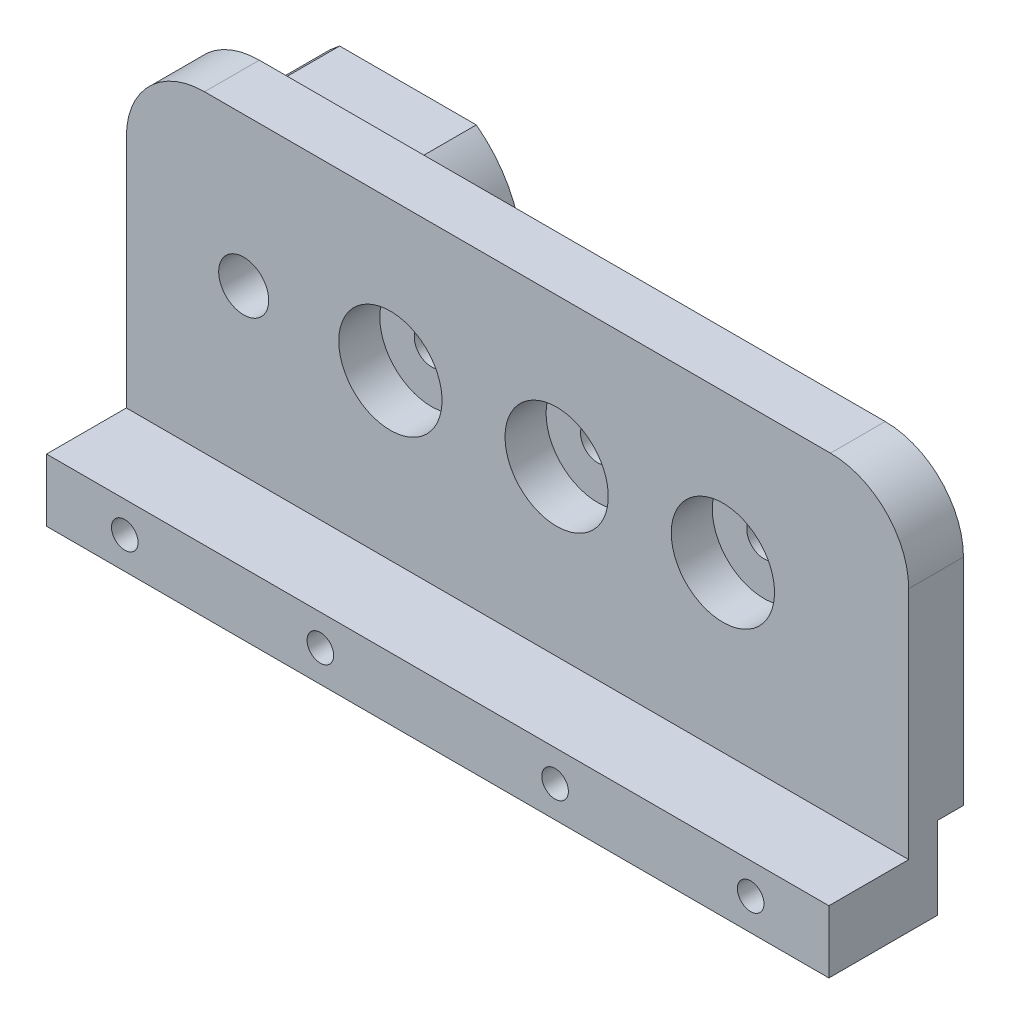
SolidWorks part; units mm, degrees
ref_plane "Front Plane" through (0, 0, 0) normal (0, 0, 1) x (1, 0, 0)
ref_plane "Top Plane" through (0, 0, 0) normal (0, 1, 0) x (1, 0, 0)
ref_plane "Right Plane" through (0, 0, 0) normal (1, 0, 0) x (0, 0, -1)
sketch "Sketch1" plane through (0, 0, 0) normal (0, 0, 1) x (1, 0, 0)
  line L1 (0, 0) -> (100, 0)
  line L2 (0, 0) -> (0, 48)
  line L3 (0, 48) -> (100, 48)
  line L4 (100, 0) -> (100, 48)
  dimension "D1" = 100
  dimension "D2" = 48
extrude "Boss-Extrude1" add sketch "Sketch1" along normal blind 7
sketch "Sketch2" plane through (0, 0, 7) normal (0, 0, 1) x (1, 0, 0)
  line L0 (0, 0) -> (100, 0) construction
  line L1 (0, 48) -> (0, 0) construction
  circle A0 centre (15, 29) radius 3.2
  circle A1 centre (33.75, 29) radius 2.2
  circle A2 centre (55, 29) radius 2.2
  circle A3 centre (76.25, 29) radius 2.2
  dimension "D1" = 4.4
  dimension "D2" = 18.75
  dimension "D3" = 21.25
  dimension "D4" = 21.25
  dimension "D5" = 29
  dimension "D6" = 15
  dimension "D7" = 6.4
extrude "Cut-Extrude1" cut sketch "Sketch2" against normal up to next
sketch "Sketch3" plane through (0, 0, 0) normal (0, 0, -1) x (-1, 0, 0)
  line L0 (0, 48) -> (0, 0) construction
  line L1 (-100, 0) -> (0, 0)
  line L2 (-100, 0) -> (-100, 8)
  line L3 (-100, 8) -> (0, 8)
  line L4 (0, 0) -> (0, 8)
  dimension "D1" = 8
extrude "Boss-Extrude2" add sketch "Sketch3" along normal blind 10.2
sketch "Sketch4" plane through (0, 0, 0) normal (0, 0, -1) x (-1, 0, 0)
  circle A0 centre (-76.25, 29) radius 6.6
  circle A1 centre (-55, 29) radius 6.6
  circle A2 centre (-33.75, 29) radius 6.6
  dimension "D1" = 13.2
extrude "Cut-Extrude2" cut sketch "Sketch4" against normal blind 5.25
sketch "Sketch5" plane through (0, 0, 7) normal (0, 0, 1) x (1, 0, 0)
  line L0 (35, 4.0521) -> (65, 4) construction
  line L1 (0, 0) -> (100, 0) construction
  circle A0 centre (35, 4.0521) radius 2.6
  circle A1 centre (65, 4) radius 2.6
  point P6 (50, 0)
  point P7 (50, 4.0261)
  dimension "D1" = 5.2
  dimension "D2" = 30
  dimension "D3" = 4
extrude "Cut-Extrude3" cut sketch "Sketch5" against normal blind 0.1
sketch "Sketch7" plane through (0, 0, 6.9) normal (0, 0, 1) x (1, 0, 0)
  circle A0 centre (35, 4.0521) radius 1.7
  circle A1 centre (65, 4) radius 1.7
  dimension "D1" = 3.4
extrude "Cut-Extrude4" cut sketch "Sketch7" against normal through all
sketch "Sketch8" plane through (0, 0, 7) normal (0, 0, 1) x (1, 0, 0)
  line L0 (10, 4.0521) -> (35, 4.0521) construction
  line L1 (0, 48) -> (0, 0) construction
  line L2 (100, 0) -> (100, 48) construction
  circle A0 centre (10, 4.0521) radius 1.7
  circle A1 centre (90, 4.0521) radius 1.7
  dimension "D1" = 3.4
  dimension "D2" = 10
  dimension "D3" = 10
extrude "Cut-Extrude5" cut sketch "Sketch8" against normal up to next
mirror "Mirror1" about plane through (0, 0, -10.2) normal (0, 0, 1) of bodies 110
delete or keep bodies "Body-Delete/Keep 1" type delete bodies bodies 110
sketch "Sketch9" plane through (100, 0, 0) normal (1, 0, 0) x (0, 0, -1)
  line L1 (27.4, 0) -> (24.1, 0)
  line L2 (27.4, 0) -> (27.4, 10.5)
  line L3 (27.4, 10.5) -> (24.1, 10.5)
  line L4 (24.1, 0) -> (24.1, 10.5)
  dimension "D1" = 10.5
  dimension "D2" = 3.3
extrude "Cut-Extrude6" cut sketch "Sketch9" against normal up to next
sketch "Sketch10" plane through (0, 0, -27.4) normal (0, 0, -1) x (-1, 0, 0)
  line L1 (-22.8594, 38.2) -> (-7.1406, 38.2)
  line L2 (-22.8594, 38.2) -> (-22.8594, 19.8) construction
  line L3 (-22.8594, 19.8) -> (-7.1406, 19.8)
  line L4 (-7.1406, 38.2) -> (-7.1406, 19.8) construction
  line L5 (-22.8594, 38.2) -> (-7.1406, 19.8) construction
  line L6 (-22.8594, 19.8) -> (-7.1406, 38.2) construction
  circle A0 centre (-15, 29) radius 12.1
  circle M6 centre (-15, 29) radius 3.2
  dimension "D2" = 24.2
  dimension "D1" = 18.4
extrude "Boss-Extrude3" add sketch "Sketch10" along normal blind 14 separate body contours L1 A0 L3 M6 | M6 region at (15, 37.896, -27.4) region at (15, 29, -27.4)
shell "Shell1" thickness 2.5 removed face at (15, 29, -27.4) removed face at (15, 29, -41.4) outward yes
combine bodies "Combine1" operation type add bodies to combine 115 116
fillet "Fillet3" radius 10 2 edges at (0, 48, -23.9) (100, 48, -23.9)
